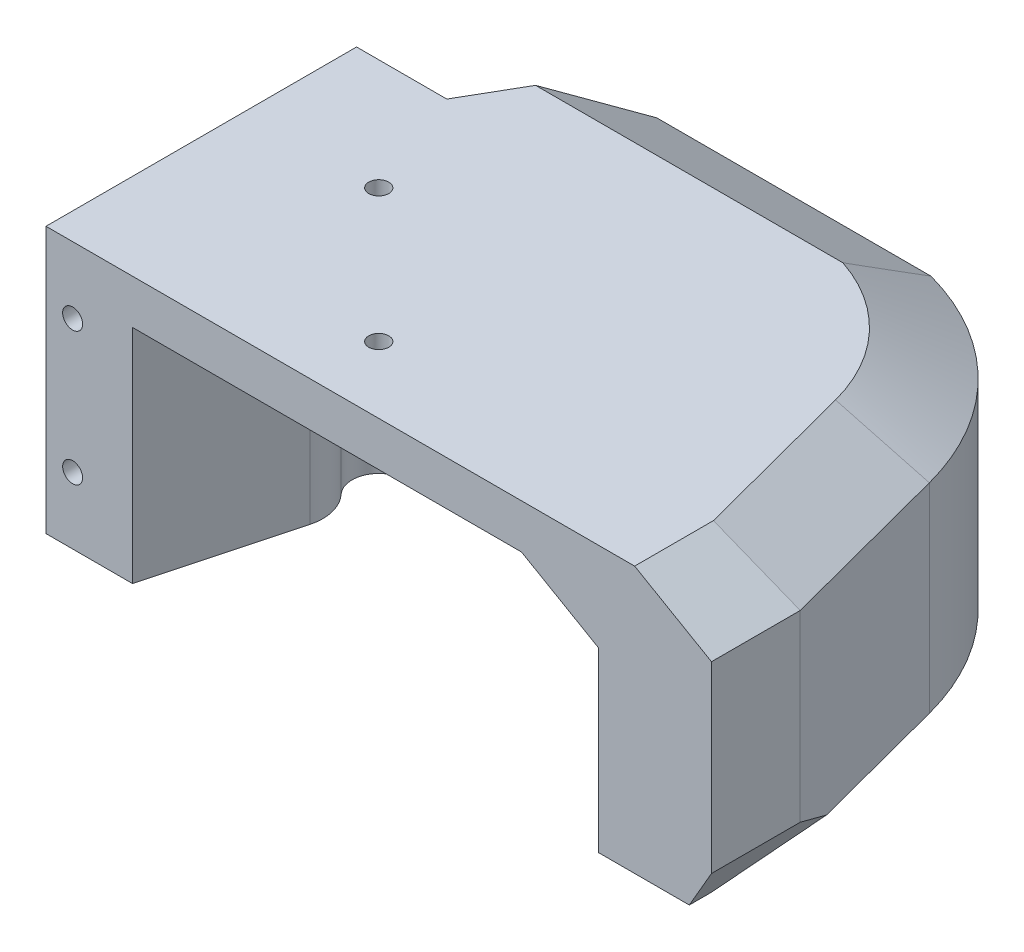
SolidWorks part; units mm, degrees
material "ABS"
ref_plane "前视基准面" through (0, 0, 0) normal (0, 0, 1) x (1, 0, 0)
ref_plane "上视基准面" through (0, 0, 0) normal (0, 1, 0) x (1, 0, 0)
ref_plane "右视基准面" through (0, 0, 0) normal (1, 0, 0) x (0, 0, -1)
other "Configuration Table"
sketch "草图1" plane through (0, 0, 0) normal (0, 0, 1) x (1, 0, 0)
  line L1 (0, 0) -> (150, 0)
  line L2 (0, 0) -> (0, 60)
  line L3 (0, 60) -> (150, 60)
  line L4 (150, 0) -> (150, 60)
  dimension "D1" = 60
  dimension "D2" = 150
extrude "凸台-拉伸1" add sketch "草图1" along normal blind 100
sketch "草图3" plane through (0, 0, 0) normal (0, -1, 0) x (1, 0, 0)
  line L0 (25.5, 100) -> (25.5, 55)
  line L1 (0, 100) -> (150, 100) construction
  line L4 (0, 100) -> (0, 0) construction
  line L6 (130.5, 100) -> (110.583, 25.6689)
  line L7 (25.5, 100) -> (130.5, 100)
  line L8 (75.8528, 16.363) -> (110.583, 25.6689)
  circle A0 centre (65.5, 55) radius 40 construction
  arc A1 (25.5, 55) -> (75.8528, 16.363) centre (65.5, 55) ccw
  dimension "D1" = 80
  dimension "D3" = 105
  dimension "D2" = 25.5
  dimension "D4" = 75
  dimension "D5" = 45
  dimension "D6" = 120
extrude "切除-拉伸3" [suppressed] cut sketch "草图3" against normal blind 50
chamfer "倒角1" [suppressed] distance 10 angle 45
sketch "草图5" plane through (0, 0, 100) normal (0, 0, 1) x (1, 0, 0)
  line L0 (6, 60) -> (6, 0) construction
  line L1 (150, 60) -> (0, 60) construction
  line L2 (0, 0) -> (150, 0) construction
  line L3 (0, 60) -> (0, 0) construction
  circle A0 centre (6, 45) radius 2.25
  circle A1 centre (6, 15) radius 2.25
  dimension "D2" = 30
  dimension "D4" = 4.5
  dimension "D1" = 6
  dimension "D3" = 15
extrude "切除-拉伸5" cut sketch "草图5" against normal through all
sketch "草图7" plane through (0, 0, 0) normal (0, -1, 0) x (1, 0, 0)
  line L0 (-4.4123, 112.6842) -> (-4.4123, 67.6842)
  line L6 (100.5877, 112.6842) -> (80.6707, 38.3532)
  line L7 (-4.4123, 112.6842) -> (100.5877, 112.6842)
  line L8 (45.9404, 29.0472) -> (80.6707, 38.3532)
  circle A0 centre (35.5877, 67.6842) radius 40 construction
  arc A1 (-4.4123, 67.6842) -> (45.9404, 29.0472) centre (35.5877, 67.6842) ccw
  dimension "D1" = 80
  dimension "D3" = 105
  dimension "D4" = 75
  dimension "D6" = 120
sketch "草图8" plane through (0, 0, 0) normal (0, -1, 0) x (1, 0, 0)
  line L0 (124.5, 100) -> (124.5, 55)
  line L1 (0, 100) -> (150, 100) construction
  line L2 (61.5569, 22.2339) -> (35.4367, 40.5235)
  line L3 (35.4367, 40.5235) -> (19.5, 100)
  line L4 (19.5, 100) -> (124.5, 100)
  line L5 (150, 100) -> (150, 0) construction
  circle A0 centre (84.5, 55) radius 40 construction
  arc A1 (61.5569, 22.2339) -> (124.5, 55) centre (84.5, 55) ccw
  line M8 (150, 100) -> (0, 100)
  dimension "D1" = 25.5
  dimension "D3" = 80
  dimension "D4" = 75
  dimension "D2" = 105
  dimension "D5" = 140
  dimension "D6" = 45
extrude "切除-拉伸7" cut sketch "草图8" against normal blind 50 contours L2 A1 L0 L3 M8
sketch "草图9" plane through (0, 0, 0) normal (0, -1, 0) x (1, 0, 0)
  line L1 (150, 100) -> (150, 0) construction
  line L2 (150, 80) -> (150, 0)
  line L3 (150, 0) -> (99.4666, 0)
  line L4 (0, 0) -> (150, 0) construction
  line L5 (139.63, 40.5195) -> (150, 80)
  line L6 (19.6215, 30) -> (27.6599, 0)
  line L7 (35.4367, 40.5235) -> (19.5, 100) construction
  line L8 (19.6215, 30) -> (0, 30)
  line L9 (0, 100) -> (0, 0) construction
  line L10 (27.6599, 0) -> (0, 0)
  line L11 (0, 30) -> (0, 0)
  arc A0 (99.4666, 0) -> (139.63, 40.5195) centre (84.5, 55) ccw
  point P15 (27.6689, 0)
  point P19 (28.6702, -3.7702)
  dimension "D1" = 114
  dimension "D2" = 80
  dimension "D3" = 18
  dimension "D4" = 30
extrude "切除-拉伸8" cut sketch "草图9" against normal through all
sketch "草图10" plane through (0, 60, 0) normal (0, 1, 0) x (1, 0, 0)
  line L0 (150, -100) -> (0, -100) construction
  line L1 (0, -100) -> (0, -30) construction
  circle A0 centre (30, -55) radius 2.25
  circle A1 centre (60, -85) radius 2.25
  dimension "D1" = 45
  dimension "D2" = 30
  dimension "D3" = 30
  dimension "D4" = 30
  dimension "D5" = 4.5
extrude "切除-拉伸9" cut sketch "草图10" against normal through all
sketch "草图11" plane through (0, 0, 0) normal (0, -1, 0) x (1, 0, 0)
  circle A0 centre (30, 55) radius 6
  dimension "D1" = 12
extrude "切除-拉伸10" cut sketch "草图11" against normal up to surface (50 mm away) up to face at (62.7231, 50, 58.5188)
fillet "圆角1" radius 10 2 edges at (32.9567, 25, 49.7791) (29.9501, 25, 60.9998)
chamfer "倒角2" distance 10 angle 60 3 edges at (48.4968, 50, 31.3787) (124.5, 50, 77.5) (102.9699, 50, 19.5196)
chamfer "倒角3" distance 10 angle 60 5 edges at (27.6599, 30, 0) (144.815, 60, 60.2597) (124.9826, 60, 14.8732) (63.5633, 60, 0) (150, 60, 90)
chamfer "倒角4" distance 5 angle 60 4 edges at (144.815, 0, 60.2597) (124.9826, 0, 14.8732) (68.5633, 0, 0) (150, 0, 90)
sketch "草图12" plane through (0, 50, 0) normal (0, -1, 0) x (1, 0, 0)
  circle A0 centre (30, 55) radius 4.5
  circle A1 centre (60, 85) radius 4.5
  dimension "D1" = 9
extrude "切除-拉伸11" cut sketch "草图12" against normal blind 3 and the other way blind 10
